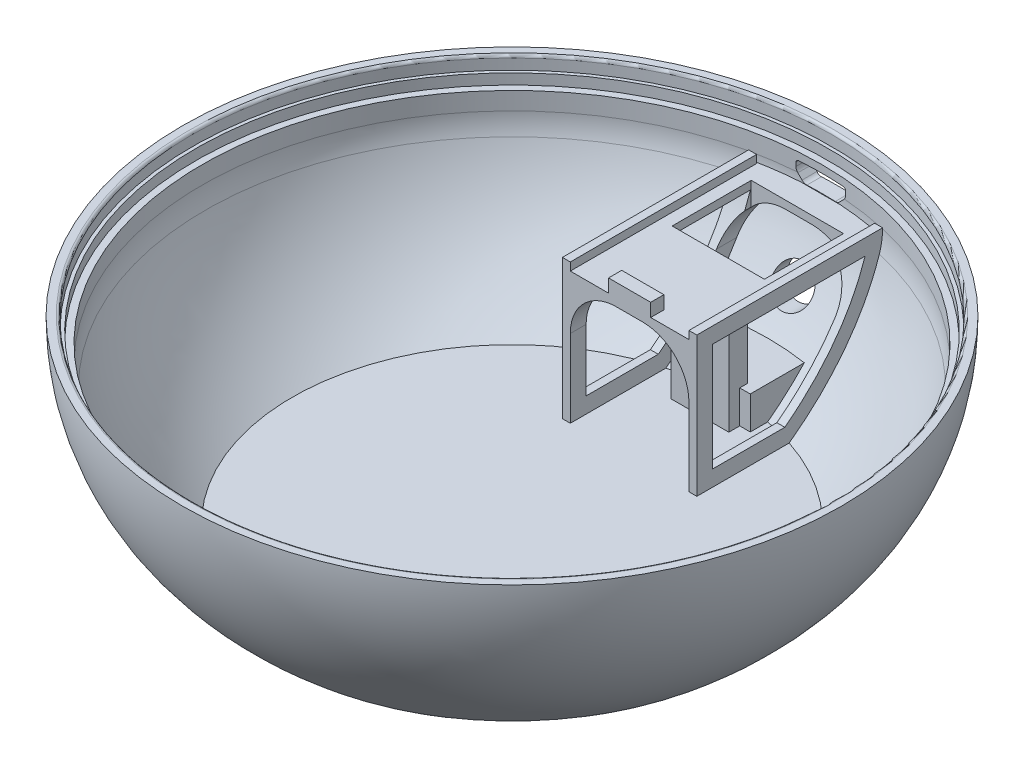
SolidWorks part; units mm, degrees
ref_plane "Plano frontal" through (0, 0, 0) normal (0, 0, 1) x (1, 0, 0)
ref_plane "Plano superior" through (0, 0, 0) normal (0, 1, 0) x (1, 0, 0)
ref_plane "Plano direito" through (0, 0, 0) normal (1, 0, 0) x (0, 0, -1)
sketch "Esboço1" plane through (0, 0, 0) normal (0, 0, 1) x (1, 0, 0)
  line L0 (0, 0) -> (0, -29.3333)
  line L1 (33.9935, -29.3333) -> (0, -29.3333)
  line L4 (0, 0) -> (50, 0)
  ellipse E0 centre (0, 0) end of major axis (-50, 0) minor radius 40 (33.9935, -29.3333) -> (50, 0) ccw
  dimension "D1" = 40
  dimension "D2" = 100
  dimension "D3" = 33.9935
revolve "Revolução1" add sketch "Esboço1" angle 360 about L0
shell "Casca1" thickness 2 removed face at (0, 0, 50)
sketch "Esboço7" plane through (0, 0, 0) normal (0, 1, 0) x (1, 0, 0)
  circle A0 centre (0, 0) radius 47
  circle A1 centre (0, 0) radius 48
  dimension "D1" = 94
extrude "Ressalto-extrusão3" add sketch "Esboço7" against normal up to next
sketch "Esboço9" plane through (0, 0, 0) normal (0, 1, 0) x (1, 0, 0)
  circle A0 centre (0, 0) radius 48.5
  dimension "D1" = 97
extrude "Corte-extrusão5" cut sketch "Esboço9" against normal blind 2
fillet "Filete3" radius 10 1 edges at (0, -7.7061, 47)
fillet "Filete4" radius 0.4 1 edges at (0, 0, 48.5)
fillet "Filete9" radius 6 1 edges at (0, -29.3333, 33.9935)
sketch "Esboço10" plane through (0, -2, 0) normal (0, 1, 0) x (1, 0, 0)
  circle A0 centre (0, 0) radius 48
  dimension "D1" = 96
extrude "Corte-extrusão6" cut sketch "Esboço10" against normal blind 1.6
sketch "Esboço15" plane through (0, 0, 0) normal (0, 0, 1) x (1, 0, 0)
  line L0 (0, -7.3333) -> (0, -4.7333) construction
  line L2 (-3.375, -4.7333) -> (3.375, -4.7333)
  line L3 (3.775, -5.1333) -> (3.775, -5.681)
  line L4 (3.4964, -6.3736) -> (2.8702, -7.0259)
  line L5 (2.1488, -7.3333) -> (-2.1488, -7.3333)
  line L6 (33.3248, -27.3333) -> (-33.3248, -27.3333) construction
  line L7 (-3.4964, -6.3736) -> (-2.8702, -7.0259)
  line L8 (-3.775, -5.1333) -> (-3.775, -5.681)
  arc A0 (2.8702, -7.0259) -> (2.1488, -7.3333) centre (2.1488, -6.3333) cw
  arc A1 (-2.8702, -7.0259) -> (-2.1488, -7.3333) centre (-2.1488, -6.3333) ccw
  arc A2 (3.775, -5.681) -> (3.4964, -6.3736) centre (2.775, -5.681) cw
  arc A3 (-3.4964, -6.3736) -> (-3.775, -5.681) centre (-2.775, -5.681) cw
  arc A4 (3.375, -4.7333) -> (3.775, -5.1333) centre (3.375, -5.1333) cw
  arc A5 (-3.775, -5.1333) -> (-3.375, -4.7333) centre (-3.375, -5.1333) cw
  point P14 (2.575, -7.3333)
  point P17 (-2.575, -7.3333)
  point P20 (3.775, -6.0833)
  point P23 (-3.775, -6.0833)
  point P26 (3.775, -4.7333)
  point P29 (-3.775, -4.7333)
  dimension "D6" = 1
  dimension "D7" = 0.4
  dimension "D1" = 7.55
  dimension "D2" = 2.6
  dimension "D3" = 1.35
  dimension "D4" = 5.15
  dimension "D5" = 20
extrude "Corte-extrusão9" cut sketch "Esboço15" against normal blind 62
ref_plane "Plano1" through (0, 0, -46.8482) normal (0, 0, -1) x (-1, 0, 0)
sketch "Esboço17" plane through (0, 0, -46.8482) normal (0, 0, -1) x (-1, 0, 0)
  line L0 (3.775, -5.681) -> (3.775, -5.1333) construction
  line L1 (10, -7.3333) -> (-10.4, -7.3333)
  line L2 (10, -7.3333) -> (10, -8.5333)
  line L3 (10, -8.5333) -> (-10.4, -8.5333)
  line L4 (-10.4, -7.3333) -> (-10.4, -8.5333)
  line L5 (-3.775, -5.1333) -> (-3.775, -5.681) construction
  line L7 (-3.375, -4.7333) -> (3.375, -4.7333) construction
  dimension "D1" = 1.2
  dimension "D2" = 6.225
  dimension "D3" = 20.4
  dimension "D4" = 2.6
  dimension "D5" = 6.625
extrude "Ressalto-extrusão4" add sketch "Esboço17" against normal blind 29.2
sketch "Esboço19" plane through (0, -8.5333, 0) normal (0, -1, 0) x (1, 0, 0)
  line L1 (-10, -17.6482) -> (-8.8, -17.6482)
  line L2 (-10, -17.6482) -> (-10, -45.9094)
  line L3 (-10, -45.9094) -> (-8.8, -45.9094)
  line L4 (-8.8, -17.6482) -> (-8.8, -45.9094)
  line L5 (10.4, -17.6482) -> (9.2, -17.6482)
  line L6 (10.4, -17.6482) -> (10.4, -45.831)
  line L7 (10.4, -45.831) -> (9.2, -45.831)
  line L8 (9.2, -17.6482) -> (9.2, -45.831)
  arc A0 (-10, -45.6631) -> (10.4, -45.5736) centre (0, 0) ccw construction
  dimension "D1" = 1.2
  dimension "D2" = 1.2
extrude "Ressalto-extrusão5" add sketch "Esboço19" along normal up to next and the other way blind 2.4
sketch "Esboço20" plane through (0, -7.3333, 0) normal (0, 1, 0) x (1, 0, 0)
  line L0 (-8.8, 17.6482) -> (9.2, 17.6482) construction
  line L1 (-3, 17.6482) -> (3.4, 17.6482)
  line L2 (-3, 17.6482) -> (-3, 19.6482)
  line L3 (-3, 19.6482) -> (3.4, 19.6482)
  line L4 (3.4, 17.6482) -> (3.4, 19.6482)
  line L5 (-10, 17.6482) -> (-10, 45.9094) construction
  point P6 (-3, 18.6482)
  dimension "D1" = 2
  dimension "D2" = 7
  dimension "D3" = 6.4
extrude "Ressalto-extrusão6" add sketch "Esboço20" along normal blind 2
fillet "Filete10" radius 7 2 edges at (9.2, -8.5333, -31.7396) (-8.8, -8.5333, -31.7788)
sketch "Esboço22" plane through (-10, 0, 0) normal (-1, 0, 0) x (0, 0, 1)
  line L4 (-30.9951, -24.9333) -> (-20.0482, -24.9333)
  line L5 (-20.0482, -24.9333) -> (-20.0482, -8.5333)
  line L6 (-20.0482, -8.5333) -> (-43.1747, -8.5333)
  line L7 (-43.1747, -8.5333) -> (-43.1747, -8.5333)
  line L8 (-31.789, -27.3333) -> (-17.6482, -27.3333)
  line L9 (-17.6482, -27.3333) -> (-17.6482, -6.1333)
  line L10 (-17.6482, -6.1333) -> (-45.9094, -6.1333)
  line L11 (-45.9094, -6.1333) -> (-45.9094, -6.8209)
  line L12 (-31.789, -27.3333) -> (-17.6482, -27.3333)
  line L13 (-17.6482, -27.3333) -> (-17.6482, -6.1333)
  line L14 (-17.6482, -6.1333) -> (-45.9094, -6.1333)
  line L15 (-45.9094, -6.1333) -> (-45.9094, -6.8209)
  spline S0 degree 1 poles (-43.1747, -8.5333) (-43.153, -8.6006) knots 0 0 1 1 construction
  spline S1 degree 1 poles (-43.153, -8.6006) (-30.9951, -24.9333) knots 0 0 1 1 construction
  spline S2 degree 3 poles (-3029.8638, 105.7128) (1378.8052, 270.2244) (-63.7694, 87.7577) (-40.427, -36.4503) (94.6861, -56.6147) (-423.7238, 2963.5881) knots -112.684195 -112.684195 -112.684195 -112.684195 0.5 0.5 33.980446 33.980446 33.980446 33.980446 only from (-45.9094, -6.8209) to (-45.4326, -9.351)
  spline S3 degree 3 poles (2457.4829, 1635.5331) (162.9448, 292.8705) (-84.0678, 61.0324) (-42.2579, -16.2752) (-41.2131, -17.87) (-39.4461, -20.1538) (-38.8282, -20.8907) (-37.5459, -22.3105) (-36.8803, -22.9948) (85.7189, -140.5061) (928.7106, 496.5601) (-1687.4677, -2483.0647) knots -11.064208 -11.064208 -11.064208 -11.064208 0.25 0.25 0.5 0.5 0.625 0.625 0.75 0.75 22.876083 22.876083 22.876083 22.876083 only from (-45.4326, -9.351) to (-31.789, -27.3333)
  spline S4 degree 3 poles (-45.9094, -6.8209) (-45.8862, -7.2477) (-45.8352, -7.6728) (-45.676, -8.5197) (-45.5675, -8.9413) (-45.4326, -9.351) knots 0 0 0 0 0.5 0.5 1 1 1 1
  spline S5 degree 3 poles (-45.4326, -9.351) (-44.8289, -11.1851) (-44.0656, -12.9326) (-42.2579, -16.2752) (-41.2131, -17.87) (-39.4461, -20.1538) (-38.8282, -20.8907) (-37.5459, -22.3105) (-36.8803, -22.9948) (-34.8141, -24.9752) (-33.3446, -26.1992) (-31.789, -27.3333) knots 0 0 0 0 0.25 0.25 0.5 0.5 0.625 0.625 0.75 0.75 1 1 1 1
  spline S6 degree 3 poles (-43.1747, -8.5333) (-43.1676, -8.5558) (-43.1603, -8.5782) (-43.153, -8.6006) knots 0.963752 0.963752 0.963752 0.963752 1 1 1 1
  spline S7 degree 3 poles (-43.153, -8.6006) (-42.0888, -11.8334) (-38.816, -17.9031) (-33.7546, -22.8432) (-30.9951, -24.9333) knots 0 0 0 0 0.482313 0.964625 0.964625 0.964625 0.964625
  dimension "D1" = 0
  dimension "D2" = 2.4
extrude "Corte-extrusão11" cut sketch "Esboço22" against normal up to surface (20.4 mm away) contours L6 L7 S6 S7 L4 L5 up to face at (10.4, -12.9495, -31.1706)
sketch "Esboço24" plane through (0, 0, 0) normal (0, 0, 1) x (1, 0, 0)
  line L1 (9.2, -27.3333) -> (10.4, -27.3333) construction
  line L2 (-10, -27.3333) -> (-8.8, -27.3333) construction
  ellipse E0 centre (0, -17.3333) end of major axis (-3, -17.3333) minor radius 2.5
  point P1 (0, 0)
  point P4 (0, 0)
  point P12 (0, 0)
  dimension "D1" = 10
  dimension "D2" = 6
  dimension "D3" = 2.5
extrude "Corte-extrusão12" cut sketch "Esboço24" against normal up to next
ref_plane "Plano2" through (0, -8.5333, 0) normal (0, -1, 0) x (-1, 0, 0)
sketch "Esboço29" plane through (0, -8.5333, 0) normal (0, -1, 0) x (-1, 0, 0)
  line L0 (0, 16.1333) -> (0, -16.1333) construction
  line L1 (4.4, 31.3) -> (-4.4, 31.3)
  line L2 (4.4, 31.3) -> (4.4, 28.5)
  line L3 (4.4, 28.5) -> (-4.4, 28.5)
  line L4 (-4.4, 31.3) -> (-4.4, 28.5)
  line L5 (4.4, 31.3) -> (-4.4, 28.5) construction
  line L6 (4.4, 28.5) -> (-4.4, 31.3) construction
  point P0 (0, 29.9)
  point P7 (-4.4, 31.6511)
  point P15 (0, 0)
  dimension "D3" = 29.9
  dimension "D1" = 8.8
  dimension "D2" = 2.8
extrude "Ressalto-extrusão11" add sketch "Esboço29" along normal up to surface (18.8 mm away) up to face at (0.1497, -27.3333, -16.8004)
sketch "Esboço30" plane through (0, -7.3333, 0) normal (0, 1, 0) x (1, 0, 0)
  line L0 (0, -16.1333) -> (0, 16.1333) construction
  line L1 (-7, 43.3) -> (7, 43.3)
  line L2 (-7, 43.3) -> (-7, 31.3)
  line L3 (-7, 31.3) -> (7, 31.3)
  line L4 (7, 43.3) -> (7, 31.3)
  line L5 (-7, 43.3) -> (7, 31.3) construction
  line L6 (-7, 31.3) -> (7, 43.3) construction
  line L8 (-4.4, 31.3) -> (4.4, 31.3) construction
  point P0 (0, 37.3)
  dimension "D1" = 14
  dimension "D2" = 12
  dimension "D3" = 0
extrude "Corte-extrusão13" cut sketch "Esboço30" against normal blind 4
sketch "Esboço27" plane through (0, 0, 0) normal (1, 0, 0) x (0, 0, -1)
  line L0 (40.7485, -22.3333) -> (30.1545, -22.3333)
  line L1 (30.1545, -22.3333) -> (30.1545, -27.3333)
  line L2 (30.1545, -27.3333) -> (33.7166, -27.7767)
  line L4 (17.6482, -27.3333) -> (31.6604, -27.3333) construction
  line L5 (33.7166, -27.7767) -> (37.7706, -25.4136)
  line L6 (37.7706, -25.4136) -> (39.1733, -23.8825)
  line L7 (39.1733, -23.8825) -> (40.7485, -22.3333)
  line L8 (40.9291, -19.8333) -> (43.4209, -19.8333) construction
  point P9 (0, 0)
  point P11 (0, 0)
  point P12 (41.7682, -20.1333)
  point P13 (0, 0)
  point P14 (0, 0)
  point P15 (39.1733, -23.8825)
  point P16 (42.2652, -20.1333)
  point P17 (40.7485, -21.3333)
  point P18 (31.3734, -27.3333)
  point P19 (30.1545, -22.3333)
  dimension "D1" = 2.5
extrude "Ressalto-extrusão9" add sketch "Esboço27" along normal blind 6 and the other way blind 6
